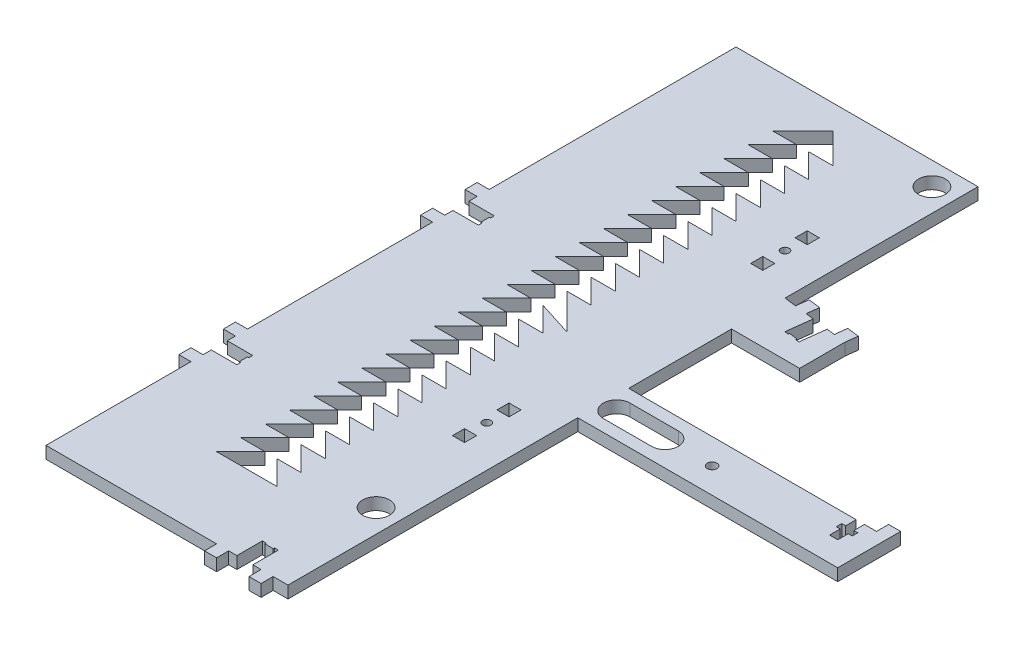
SolidWorks part; units mm, degrees
ref_plane "Front Plane" through (0, 0, 0) normal (0, 0, 1) x (1, 0, 0)
ref_plane "Top Plane" through (0, 0, 0) normal (0, 1, 0) x (1, 0, 0)
ref_plane "Right Plane" through (0, 0, 0) normal (1, 0, 0) x (0, 0, -1)
sketch "Axle Support Plate" plane through (0, 0, 0) normal (0, 1, 0) x (1, 0, 0)
  line L0 (51.4759, 169.2049) -> (51.4759, -122.8951) construction
  line L1 (38.7759, 181.3151) -> (38.7759, -110.5692) construction
  line L2 (0, 168.6151) -> (-15.875, 152.7401)
  line L3 (-15.875, 152.7401) -> (-3.175, 152.7401)
  line L4 (63.5861, -181.3151) -> (63.5861, -102.2391)
  line L5 (-63.5861, 181.3151) -> (63.5861, -181.3151) construction
  line L6 (-63.5861, -181.3151) -> (63.5861, 181.3151) construction
  line L7 (-63.5861, -75.3971) -> (-63.5861, 21.8849)
  line L8 (-63.5861, 181.3151) -> (63.5861, 181.3151)
  line L9 (0, 181.3151) -> (0, -181.3151) construction
  line L10 (15.875, 152.7401) -> (0, 168.6151)
  line L11 (-3.175, 152.7401) -> (-15.875, 140.0401)
  line L12 (-15.875, 140.0401) -> (-3.175, 140.0401)
  line L13 (15.875, 140.0401) -> (3.175, 152.7401)
  line L14 (-3.175, 140.0401) -> (-15.875, 127.3401)
  line L15 (-15.875, 127.3401) -> (-3.175, 127.3401)
  line L16 (15.875, 127.3401) -> (3.175, 140.0401)
  line L17 (63.5861, 23.1549) -> (8.1203, 23.1549) construction
  line L18 (-3.175, 127.3401) -> (-15.875, 114.6401)
  line L19 (-15.875, 114.6401) -> (-3.175, 114.6401)
  line L20 (15.875, 114.6401) -> (3.175, 127.3401)
  line L21 (-3.175, 114.6401) -> (-15.875, 101.9401)
  line L22 (-15.875, 101.9401) -> (-3.175, 101.9401)
  line L23 (55.7939, -181.3151) -> (63.5861, -181.3151)
  line L24 (15.875, 101.9401) -> (3.175, 114.6401)
  line L25 (-3.175, 101.9401) -> (-15.875, 89.2401)
  line L26 (-15.875, 89.2401) -> (-3.175, 89.2401)
  line L27 (15.875, 89.2401) -> (3.175, 101.9401)
  line L28 (-3.175, 89.2401) -> (-15.875, 76.5401)
  line L29 (-15.875, 76.5401) -> (-3.175, 76.5401)
  line L30 (15.875, 76.5401) -> (3.175, 89.2401)
  line L31 (-3.175, 76.5401) -> (-15.875, 63.8401)
  line L32 (-15.875, 63.8401) -> (-3.175, 63.8401)
  line L33 (15.875, 63.8401) -> (3.175, 76.5401)
  line L34 (-3.175, 63.8401) -> (-15.875, 51.1401)
  line L35 (-15.875, 51.1401) -> (-3.175, 51.1401)
  line L36 (15.875, 51.1401) -> (3.175, 63.8401)
  line L37 (63.5861, -2.2451) -> (183.1382, -2.2451)
  line L38 (172.2162, -2.2451) -> (172.2162, -29.0053) construction
  line L39 (200.1562, -29.0053) -> (63.5861, -29.0053)
  line L40 (70.6162, -15.6252) -> (96.0162, -15.6252) construction
  line L41 (70.6162, -8.5951) -> (96.0162, -8.5951)
  line L42 (70.6162, -22.6553) -> (96.0162, -22.6553)
  line L43 (63.5861, -15.6252) -> (200.1562, -15.6252) construction
  line L44 (187.4562, -2.2451) -> (193.8062, -2.2451)
  line L46 (63.5861, -2.2451) -> (63.5861, 181.3151)
  line L47 (63.5861, -2.2451) -> (63.5861, -29.0053) construction
  line L49 (-3.175, 51.1401) -> (-15.875, 38.4401)
  line L50 (-15.875, 38.4401) -> (-3.175, 38.4401)
  line L51 (200.1562, -2.2451) -> (200.1562, -29.0053)
  line L52 (15.875, 38.4401) -> (3.175, 51.1401)
  line L53 (-3.175, 38.4401) -> (-15.875, 25.7401)
  line L54 (-15.875, 25.7401) -> (-3.175, 25.7401)
  line L55 (15.875, 25.7401) -> (3.175, 38.4401)
  line L56 (-3.175, 25.7401) -> (-15.875, 13.0401)
  line L57 (-15.875, 13.0401) -> (-3.175, 13.0401)
  line L58 (21.7488, 7.1663) -> (3.175, 25.7401)
  line L59 (3.175, 0.3401) -> (15.875, 0.3401)
  line L60 (-15.875, 0.3401) -> (-3.175, 0.3401)
  line L61 (15.875, 0.3401) -> (3.175, 13.0401)
  line L62 (-3.175, 0.3401) -> (-15.875, -12.3599)
  line L63 (-15.875, -12.3599) -> (-3.175, -12.3599)
  line L64 (15.875, -12.3599) -> (3.175, 0.3401)
  line L65 (-3.175, -12.3599) -> (-15.875, -25.0599)
  line L66 (-15.875, -25.0599) -> (-3.175, -25.0599)
  line L67 (15.875, -25.0599) -> (3.175, -12.3599)
  line L68 (-3.175, -25.0599) -> (-15.875, -37.7599)
  line L69 (-15.875, -37.7599) -> (-3.175, -37.7599)
  line L70 (15.875, -37.7599) -> (3.175, -25.0599)
  line L71 (-3.175, -37.7599) -> (-15.875, -50.4599)
  line L72 (-15.875, -50.4599) -> (-3.175, -50.4599)
  line L73 (15.875, -50.4599) -> (3.175, -37.7599)
  line L74 (-3.175, -50.4599) -> (-15.875, -63.1599)
  line L75 (-15.875, -63.1599) -> (-3.175, -63.1599)
  line L76 (15.875, -63.1599) -> (3.175, -50.4599)
  line L77 (-3.175, -63.1599) -> (-15.875, -75.8599)
  line L78 (-15.875, -75.8599) -> (-3.175, -75.8599)
  line L79 (15.875, -75.8599) -> (3.175, -63.1599)
  line L80 (-3.175, -75.8599) -> (-15.875, -88.5599)
  line L81 (-63.5861, 51.6029) -> (-63.5861, 181.3151)
  line L82 (-15.875, -88.5599) -> (-3.175, -88.5599)
  line L83 (15.875, -88.5599) -> (3.175, -75.8599)
  line L84 (-3.175, -88.5599) -> (-15.875, -101.2599)
  line L85 (-15.875, -101.2599) -> (-3.175, -101.2599)
  line L86 (15.875, -101.2599) -> (3.175, -88.5599)
  line L87 (-3.175, -101.2599) -> (-15.875, -113.9599)
  line L88 (-15.875, -113.9599) -> (-3.175, -113.9599)
  line L89 (15.875, -113.9599) -> (3.175, -101.2599)
  line L90 (26.0759, -181.3151) -> (-63.5861, -181.3151)
  line L91 (-3.175, -113.9599) -> (-15.875, -126.6599)
  line L92 (-15.875, -126.6599) -> (-3.175, -126.6599)
  line L93 (15.875, -126.6599) -> (3.175, -113.9599)
  line L94 (-63.5861, -181.3151) -> (-63.5861, -105.1151)
  line L95 (-3.175, -126.6599) -> (-15.875, -139.3599)
  line L96 (-15.875, -139.3599) -> (15.875, -139.3599)
  line L97 (15.875, -139.3599) -> (3.175, -126.6599)
  line L98 (3.175, 152.7401) -> (15.875, 152.7401)
  line L99 (3.175, 127.3401) -> (15.875, 127.3401)
  line L100 (3.175, 140.0401) -> (15.875, 140.0401)
  line L101 (3.175, 114.6401) -> (15.875, 114.6401)
  line L102 (3.175, 89.2401) -> (15.875, 89.2401)
  line L103 (3.175, 101.9401) -> (15.875, 101.9401)
  line L104 (3.175, 76.5401) -> (15.875, 76.5401)
  line L105 (3.175, 63.8401) -> (15.875, 63.8401)
  line L106 (3.175, 51.1401) -> (15.875, 51.1401)
  line L107 (3.175, 38.4401) -> (15.875, 38.4401)
  line L108 (3.175, 25.7401) -> (15.875, 25.7401)
  line L109 (3.175, 13.0401) -> (21.7488, 7.1663)
  line L110 (-3.175, 13.0401) -> (-15.875, 0.3401)
  line L111 (-5.8737, 10.3413) -> (-7.0922, 9.1229) [skipped]
  line L112 (3.175, -12.3599) -> (15.875, -12.3599)
  line L113 (3.175, -25.0599) -> (15.875, -25.0599)
  line L114 (3.175, -37.7599) -> (15.875, -37.7599)
  line L115 (3.175, -50.4599) -> (15.875, -50.4599)
  line L116 (3.175, -63.1599) -> (15.875, -63.1599)
  line L117 (3.175, -75.8599) -> (15.875, -75.8599)
  line L118 (3.175, -88.5599) -> (15.875, -88.5599)
  line L119 (3.175, -101.2599) -> (15.875, -101.2599)
  line L120 (3.175, -113.9599) -> (15.875, -113.9599)
  line L121 (3.175, -126.6599) -> (15.875, -126.6599)
  line L125 (63.5861, -102.2391) -> (63.5861, -29.0053)
  line L126 (-63.5861, -216.8751) -> (63.5861, -216.8751) construction
  circle A0 centre (51.4759, 169.2049) radius 7.0301
  circle A1 centre (51.4759, -122.8951) radius 7.0301
  circle A2 centre (51.4759, -122.8951) radius 12.7 construction
  circle A3 centre (120.7812, -15.6252) radius 2.54
  arc A4 (70.6162, -8.5951) -> (70.6162, -22.6553) centre (70.6162, -15.6252) ccw
  arc A5 (96.0162, -22.6553) -> (96.0162, -8.5951) centre (96.0162, -15.6252) ccw
  circle A6 centre (96.0162, -15.6252) radius 15.875 construction
  point P8 (0, 0)
  point P15 (51.4759, 23.1549)
  point P57 (83.3162, -15.6252)
  point P144 (64.1759, -122.8951)
  point P145 (51.4759, -135.5951)
  point P146 (111.8912, -15.6252)
  point P147 (118.2412, -15.6252)
  line B0 (-63.5861, -81.7471) -> (-69.9361, -81.7471)
  line B1 (-69.9361, -81.7471) -> (-69.9361, -75.3971)
  line B2 (-69.9361, -75.3971) -> (-63.5861, -75.3971)
  line B3 (-63.5861, -88.0971) -> (-64.2662, -88.0971)
  line B4 (-64.2662, -88.0971) -> (-64.2662, -86.0561)
  line B5 (-64.2662, -86.0561) -> (-50.2059, -86.0561)
  line B6 (-50.2059, -86.0561) -> (-50.2059, -88.0971)
  line B7 (-50.2059, -88.0971) -> (-50.8861, -88.0971)
  line B8 (-50.8861, -88.0971) -> (-50.8861, -92.4151)
  line B9 (-50.8861, -92.4151) -> (-50.2059, -92.4151)
  line B10 (-50.2059, -92.4151) -> (-50.2059, -94.4561)
  line B11 (-50.2059, -94.4561) -> (-64.2662, -94.4561)
  line B12 (-64.2662, -94.4561) -> (-64.2662, -92.4151)
  line B13 (-64.2662, -92.4151) -> (-63.5861, -92.4151)
  line B14 (-50.8861, -90.2561) -> (-63.5861, -90.2561) construction
  line B15 (-63.5861, -98.7651) -> (-63.5861, -92.4151)
  line B16 (-69.9361, -105.1151) -> (-63.5861, -105.1151)
  line B17 (-63.5861, -81.7471) -> (-63.5861, -88.0971)
  line B18 (-69.9361, -98.7651) -> (-69.9361, -105.1151)
  line B19 (-63.5861, -98.7651) -> (-69.9361, -98.7651)
  line B20 (-63.5861, 45.2529) -> (-69.9361, 45.2529)
  line B21 (-69.9361, 45.2529) -> (-69.9361, 51.6029)
  line B22 (-69.9361, 51.6029) -> (-63.5861, 51.6029)
  line B23 (-63.5861, 38.9029) -> (-64.2662, 38.9029)
  line B24 (-64.2662, 38.9029) -> (-64.2662, 40.9439)
  line B25 (-64.2662, 40.9439) -> (-50.2059, 40.9439)
  line B26 (-50.2059, 40.9439) -> (-50.2059, 38.9029)
  line B27 (-50.2059, 38.9029) -> (-50.8861, 38.9029)
  line B28 (-50.8861, 38.9029) -> (-50.8861, 34.5849)
  line B29 (-50.8861, 34.5849) -> (-50.2059, 34.5849)
  line B30 (-50.2059, 34.5849) -> (-50.2059, 32.5439)
  line B31 (-50.2059, 32.5439) -> (-64.2662, 32.5439)
  line B32 (-64.2662, 32.5439) -> (-64.2662, 34.5849)
  line B33 (-64.2662, 34.5849) -> (-63.5861, 34.5849)
  line B34 (-50.8861, 36.7439) -> (-63.5861, 36.7439) construction
  line B35 (-63.5861, 28.2349) -> (-63.5861, 34.5849)
  line B36 (-69.9361, 21.8849) -> (-63.5861, 21.8849)
  line B37 (-63.5861, 45.2529) -> (-63.5861, 38.9029)
  line B38 (-69.9361, 28.2349) -> (-69.9361, 21.8849)
  line B39 (-63.5861, 28.2349) -> (-69.9361, 28.2349)
  line B40 (32.4259, -181.3151) -> (32.4259, -187.6651)
  line B41 (32.4259, -187.6651) -> (26.0759, -187.6651)
  line B42 (26.0759, -187.6651) -> (26.0759, -181.3151)
  line B43 (38.7759, -181.3151) -> (38.7759, -181.9952)
  line B44 (38.7759, -181.9952) -> (36.7349, -181.9952)
  line B45 (36.7349, -181.9952) -> (36.7349, -167.9349)
  line B46 (36.7349, -167.9349) -> (38.7759, -167.9349)
  line B47 (38.7759, -167.9349) -> (38.7759, -168.6151)
  line B48 (38.7759, -168.6151) -> (43.0939, -168.6151)
  line B49 (43.0939, -168.6151) -> (43.0939, -167.9349)
  line B50 (43.0939, -167.9349) -> (45.1349, -167.9349)
  line B51 (45.1349, -167.9349) -> (45.1349, -181.9952)
  line B52 (45.1349, -181.9952) -> (43.0939, -181.9952)
  line B53 (43.0939, -181.9952) -> (43.0939, -181.3151)
  line B54 (40.9349, -168.6151) -> (40.9349, -181.3151) construction
  line B55 (49.4439, -181.3151) -> (43.0939, -181.3151)
  line B56 (55.7939, -187.6651) -> (55.7939, -181.3151)
  line B57 (32.4259, -181.3151) -> (38.7759, -181.3151)
  line B58 (49.4439, -187.6651) -> (55.7939, -187.6651)
  line B59 (49.4439, -181.3151) -> (49.4439, -187.6651)
  line B60 (41.9509, 86.6549) -> (41.9509, 116.3729) construction
  line B61 (39.7919, 101.5139) -> (44.1099, 101.5139) construction
  line B62 (38.7759, 110.0229) -> (45.1259, 110.0229)
  line B63 (38.7759, 110.0229) -> (38.7759, 116.3729)
  line B64 (38.7759, 116.3729) -> (45.1259, 116.3729)
  line B65 (45.1259, 110.0229) -> (45.1259, 116.3729)
  line B66 (38.7759, 110.0229) -> (45.1259, 116.3729) construction
  line B67 (38.7759, 116.3729) -> (45.1259, 110.0229) construction
  line B68 (38.7759, 86.6549) -> (45.1259, 93.0049) construction
  line B69 (38.7759, 93.0049) -> (45.1259, 86.6549) construction
  line B70 (45.1259, 93.0049) -> (45.1259, 86.6549)
  line B71 (38.7759, 86.6549) -> (45.1259, 86.6549)
  line B72 (38.7759, 93.0049) -> (38.7759, 86.6549)
  line B73 (38.7759, 93.0049) -> (45.1259, 93.0049)
  circle B74 centre (41.9509, 101.5139) radius 2.159
  line B75 (41.9509, -40.3451) -> (41.9509, -70.0631) construction
  line B76 (39.7919, -55.2041) -> (44.1099, -55.2041) construction
  line B77 (38.7759, -63.7131) -> (45.1259, -63.7131)
  line B78 (38.7759, -63.7131) -> (38.7759, -70.0631)
  line B79 (38.7759, -70.0631) -> (45.1259, -70.0631)
  line B80 (45.1259, -63.7131) -> (45.1259, -70.0631)
  line B81 (38.7759, -63.7131) -> (45.1259, -70.0631) construction
  line B82 (38.7759, -70.0631) -> (45.1259, -63.7131) construction
  line B83 (38.7759, -40.3451) -> (45.1259, -46.6951) construction
  line B84 (38.7759, -46.6951) -> (45.1259, -40.3451) construction
  line B85 (45.1259, -46.6951) -> (45.1259, -40.3451)
  line B86 (38.7759, -40.3451) -> (45.1259, -40.3451)
  line B87 (38.7759, -46.6951) -> (38.7759, -40.3451)
  line B88 (38.7759, -46.6951) -> (45.1259, -46.6951)
  circle B89 centre (41.9509, -55.2041) radius 2.159
  line B90 (187.4562, -2.2451) -> (187.4562, -7.7801)
  line B91 (187.4562, -7.7801) -> (189.4972, -7.7801)
  line B92 (189.4972, -7.7801) -> (189.4972, -10.6801)
  line B93 (189.4972, -10.6801) -> (187.4562, -10.6801)
  line B94 (187.4562, -10.6801) -> (187.4562, -16.2151)
  line B95 (187.4562, -16.2151) -> (183.1382, -16.2151)
  line B96 (183.1382, -16.2151) -> (183.1382, -10.6801)
  line B97 (183.1382, -10.6801) -> (181.0972, -10.6801)
  line B98 (181.0972, -10.6801) -> (181.0972, -7.7801)
  line B99 (181.0972, -7.7801) -> (183.1382, -7.7801)
  line B100 (183.1382, -7.7801) -> (183.1382, -2.2451)
  line B101 (193.8062, -2.2451) -> (193.8062, 4.1049)
  line B102 (193.8062, 4.1049) -> (200.1562, 4.1049)
  line B103 (200.1562, 4.1049) -> (200.1562, -2.2451)
  dimension "D1" = 5.08
  dimension "D4" = 14.0603
  dimension "D5" = 5.08
  dimension "D8" = 31.75
  dimension "D14" = 14.0603
  dimension "D15" = 5.08
  dimension "D16" = 31.75
  dimension "D22" = 7.0301
  dimension "D25" = 6.35
  dimension "D13" = 25.4
  dimension "D19" = 81.28
  dimension "D21" = 76.2
  dimension "D2" = 292.1
  dimension "D6" = 12.7
  dimension "D7" = 63.5
  dimension "D9" = 89.662
  dimension "D10" = 12.7
  dimension "D11" = 24
  dimension "D12" = 10.541
  dimension "D17" = 6.35
  dimension "D18" = 35.56
  dimension "D20" = 27.94
  dimension "D23" = 6.35
  dimension "D24" = 25.4
  dimension "D26" = 25.4
  dimension "D27" = 6.35
  dimension "D29" = 76.2
  dimension "D30" = 203.2
sketch_block_instance "Male T-slot assembly-1"
sketch_block "Male T-slot assembly" parameters "D1"=6.35, "D2"=6.35, "D3"=4.318, "D4"=14.0603, "D5"=8.4, "D6"=12.7, "D7"=6.35
sketch_block_instance "Male T-slot assembly-2"
sketch_block_instance "Male T-slot assembly-4"
sketch_block_instance "Female T-Slot Assembly-1"
sketch_block "Female T-Slot Assembly" parameters "D4"=4.318, "D1"=6.35, "D2"=6.35, "D3"=6.35
sketch_block_instance "Female T-Slot Assembly-3"
sketch_block_instance "Block-T-Slot_2-1"
sketch_block "Block-T-Slot_2" parameters "D1"=4.318, "D2"=2.9, "D3"=8.4, "D4"=13.97
sketch_block_instance "Block-T-slot_Tab-3"
sketch_block "Block-T-slot_Tab" parameters "D1"=6.35, "D2"=6.35
extrude "Boss-Extrude1" add sketch "Axle Support Plate" along normal blind 6.35 contours L23 L4 L39 L51 L37 L46 L8 region at (9.5272, 0, 2.8879)
sketch "Sketch1" plane through (0, 6.35, 0) normal (0, 1, 0) x (1, 0, 0)
  line L0 (63.5861, -2.2451) -> (63.5861, 181.3151) construction
  line L1 (99.3852, 75.5272) -> (99.3852, 51.7696)
  line L2 (99.3852, 51.7696) -> (63.5861, 51.7696)
  line L3 (44.4458, 169.2049) -> (58.5061, 169.2049) construction
  line L4 (51.4759, 176.2351) -> (51.4759, 162.1748) construction
  line L5 (69.8887, 79.1489) -> (63.5861, 79.9228)
  line L6 (63.5861, 79.9228) -> (63.5861, 51.7696)
  line L8 (63.5861, 79.9228) -> (64.3599, 86.2255) construction
  line L9 (-63.5861, 55.1589) -> (63.5861, 55.1589) construction
  line L10 (-63.5861, 51.6029) -> (-63.5861, 181.3151) construction
  line L11 (55.7939, -181.3151) -> (63.5861, -181.3151) construction
  line L12 (99.3852, 75.5272) -> (265.2714, 55.1589) construction
  line L13 (63.5861, 55.1589) -> (265.2714, 55.1589) construction
  circle A0 centre (51.4759, 169.2049) radius 7.0301 construction
  point P12 (51.4759, 169.2049)
  point P21 (59.69, -181.3151)
  line B0 (93.0826, 76.3011) -> (93.8564, 82.6037)
  line B1 (93.8564, 82.6037) -> (100.1591, 81.8299)
  line B2 (100.1591, 81.8299) -> (99.3852, 75.5272)
  line B3 (86.7799, 77.0749) -> (86.8628, 77.75)
  line B4 (86.8628, 77.75) -> (88.8886, 77.5013)
  line B5 (88.8886, 77.5013) -> (87.175, 63.5458)
  line B6 (87.175, 63.5458) -> (85.1493, 63.7945)
  line B7 (85.1493, 63.7945) -> (85.2321, 64.4696)
  line B8 (85.2321, 64.4696) -> (80.9463, 64.9958)
  line B9 (80.9463, 64.9958) -> (80.8634, 64.3208)
  line B10 (80.8634, 64.3208) -> (78.8377, 64.5695)
  line B11 (78.8377, 64.5695) -> (80.5512, 78.525)
  line B12 (80.5512, 78.525) -> (82.577, 78.2762)
  line B13 (82.577, 78.2762) -> (82.4941, 77.6012)
  line B14 (83.0892, 64.7327) -> (84.637, 77.3381) construction
  line B15 (76.1914, 78.375) -> (82.4941, 77.6012)
  line B16 (70.6626, 85.4516) -> (69.8887, 79.1489)
  line B17 (93.0826, 76.3011) -> (86.7799, 77.0749)
  line B18 (76.9653, 84.6777) -> (70.6626, 85.4516)
  line B19 (76.1914, 78.375) -> (76.9653, 84.6777)
  dimension "D1" = 7
  dimension "D2" = 12.7
  dimension "D3" = 203.2
  dimension "D4" = 6.35
  dimension "D5" = 236.474
sketch_block_instance "Male T-slot assembly-9"
extrude "Boss-Extrude2" add sketch "Sketch1" against normal blind 6.35 contours B15 B19 B18 B16 L6 L2 L1 B2 B1 B0 B17 B3 B4 B5 B6 B7 B8 B9 B10 B11 B12 B13 region at (98.888, 6.35, -63.6484)
equation "\"Ball Diameter\"= 1.75in"
equation "\"Sheet Thickness\"= 0.25in"
equation "\"Screw Diameter\"= .17in"
equation "\"Robot Diameter\"= 14in"
equation "\"Castor Screw Diameter\"= 0.22in"
equation "\"Wheel Diameter\" = 4in"
equation "\"Nut Diameter\" = 8.4mm"
equation "\"Nut Height\" = 2.9mm"
equation "\"Screw Height\" = 0.55in"
equation "\"Pulley Diameter\" = 1in"
equation "\"Reactor Height\" = 14in"
equation "\"Elevator Height\" = 11.5in"
equation "\"Elevator Width\" = \"Ball Diameter\" + 0.25in"
equation "\"D1@Boss-Extrude1\"=\"Sheet Thickness\""
equation "\"Elevator Bearing Diameter\" = sqr(2*(\"Sheet Thickness\"^2)) + 0.2in"
equation "\"Elevator Axle Length\" = \"Elevator Width\" + 8*\"Sheet Thickness\""
equation "\"D4@Male T-slot assembly\"=\"Elevator Bearing Diameter\""
equation "\"D6@Male T-slot assembly\"=(\"Pulley Diameter\")/2"
equation "\"D13@Axle Support Plate\"=\"Pulley Diameter\""
equation "\"D9@Axle Support Plate\"=\"Elevator Clearance from Axis\" + \"Sheet Thickness\""
equation "\"D14@Axle Support Plate\" = \"Elevator Bearing Diameter\""
equation "\"D22@Axle Support Plate\"=\"Elevator Bearing Diameter\"/2"
equation "\"D23@Axle Support Plate\" = \"Sheet Thickness\""
equation "\"Elevator Axle Endcap Diameter\" = \"Pulley Diameter\" + 0.25in"
equation "\"D27@Axle Support Plate\"=\"Sheet Thickness\""
equation "\"Elevator Clearance from Axis\" = 3.28in"
equation "\"D3@Sketch1\"=\"Length of Chute\""
equation "\"Ball Radius\" = \"Ball Diameter\"/2"
equation "\"Elevator Horizontal Clearance\" = \"Elevator Width\" + 0.5in"
equation "\"Claw Horizontal Seperation\" = (\"Elevator Width\"/2) - (1.5 * \"Sheet Thickness\") - 0.15in"
equation "\"Claw Radius\" = \"Ball Radius\" + 0.1in"
equation "\"Castor Wheel Height\" = 1.25in"
equation "\"Length of Chute\" = 8in"
equation "\"D16@Axle Support Plate\"=\"Elevator Axle Endcap Diameter\""
